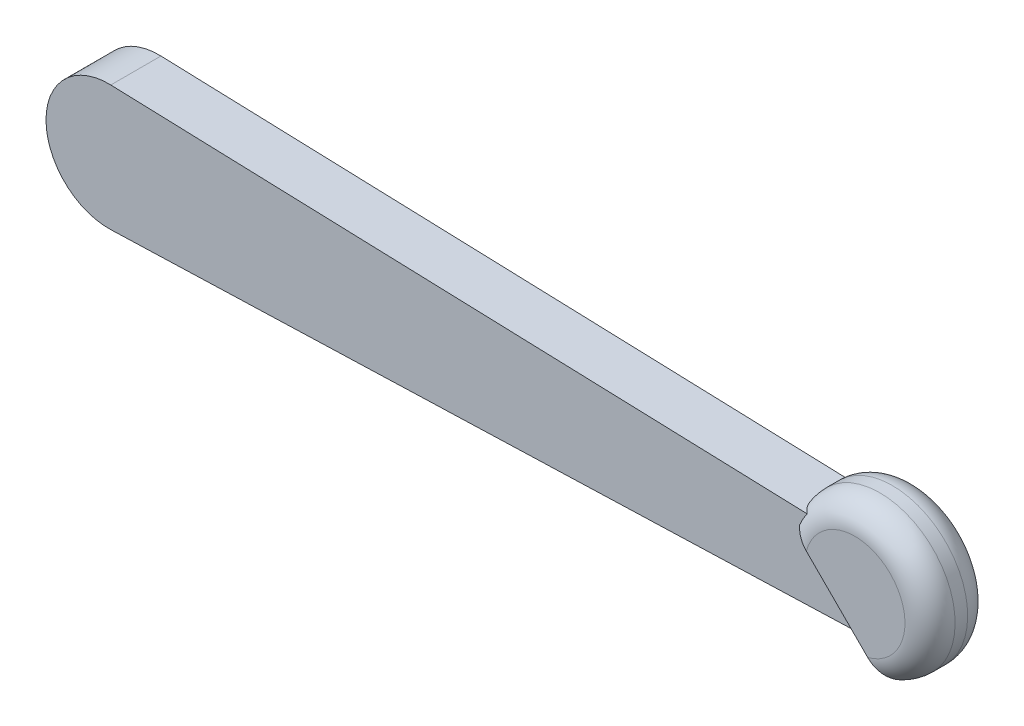
SolidWorks part; units mm, degrees
ref_plane "Спереди" through (0, 0, 0) normal (0, 0, 1) x (1, 0, 0)
ref_plane "Сверху" through (0, 0, 0) normal (0, 1, 0) x (1, 0, 0)
ref_plane "Справа" through (0, 0, 0) normal (1, 0, 0) x (0, 0, -1)
other "Configuration Table"
sketch "Эскиз1" plane through (0, 0, 0) normal (0, 0, 1) x (1, 0, 0)
  line L0 (-1416.6421, 0) -> (69415.4626, 0) construction
  line L1 (0.8333, 24.9861) -> (300.5, 14.9917)
  line L2 (0.8333, -24.9861) -> (300.5, -14.9917)
  arc A0 (0.8333, 24.9861) -> (0.8333, -24.9861) centre (0, 0) ccw
  arc A1 (300.5, -14.9917) -> (300.5, 14.9917) centre (300, 0) ccw
  arc A2 (0.8333, -24.9861) -> (25, 0) centre (0, 0) ccw construction
  arc A3 (25, 0) -> (0.8333, 24.9861) centre (0, 0) ccw construction
  arc A4 (300.5, 14.9917) -> (285, 0) centre (300, 0) ccw construction
  arc A5 (285, 0) -> (300.5, -14.9917) centre (300, 0) ccw construction
  dimension "D1" = 50
  dimension "D2" = 30
  dimension "D3" = 300
extrude "Бобышка-Вытянуть1" add sketch "Эскиз1" along normal mid plane 20
sketch "Эскиз2" plane through (0, 0, 0) normal (0, 0, 1) x (1, 0, 0)
  line L0 (-1000, 0) -> (49000, 0) construction
  line L1 (312.9289, -27.0711) -> (272.9289, 12.9289)
  arc A0 (312.9289, -27.0711) -> (272.9289, 12.9289) centre (300, 0) ccw
  arc A1 (270, 0) -> (312.9289, -27.0711) centre (300, 0) ccw construction
  arc A2 (272.9289, 12.9289) -> (270, 0) centre (300, 0) ccw construction
  dimension "D1" = 60
  dimension "D2" = 45
  dimension "D3" = 10
extrude "Бобышка-Вытянуть2" add sketch "Эскиз2" along normal mid plane 25
fillet "Скругление1" radius 10 2 edges at (321.2132, 21.2132, -12.5) (321.2132, 21.2132, 12.5)
